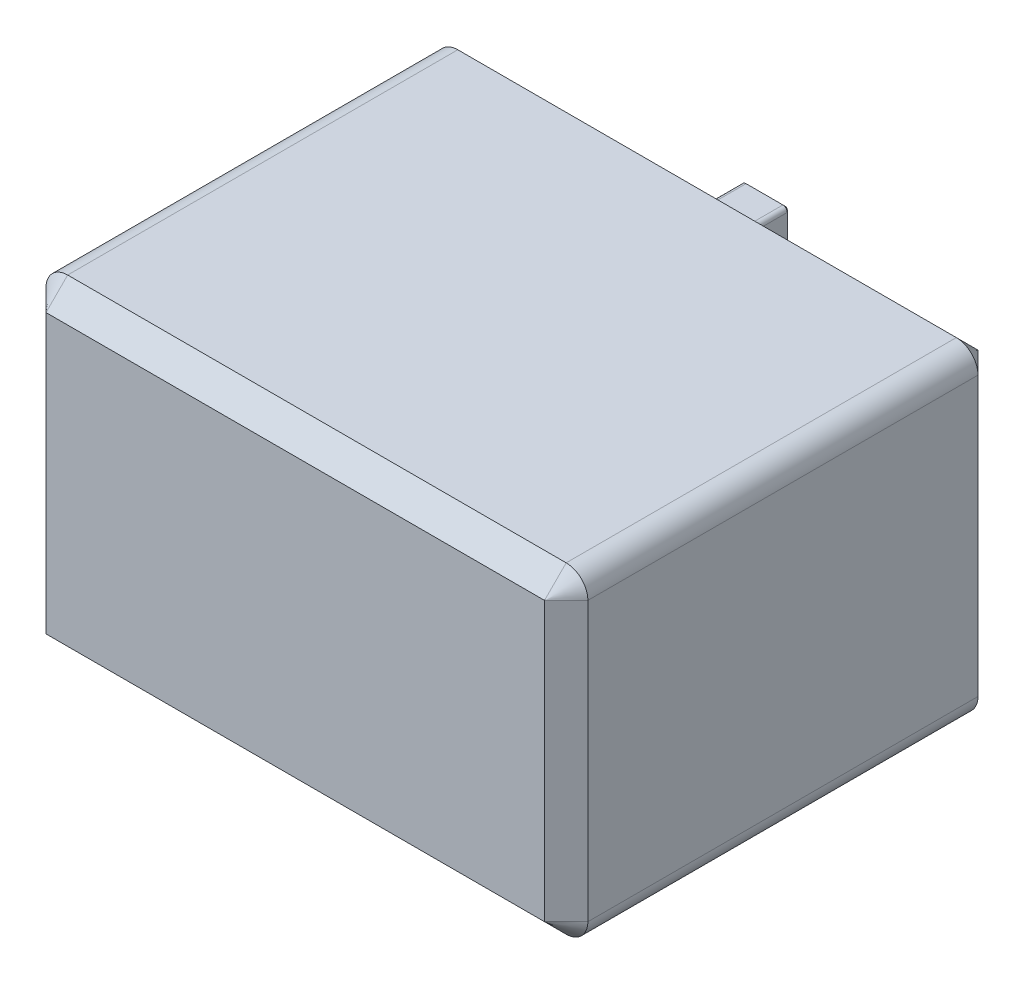
SolidWorks part; units mm, degrees
material "6061 Alloy"
ref_plane "Front Plane" through (0, 0, 0) normal (0, 0, 1) x (1, 0, 0)
ref_plane "Top Plane" through (0, 0, 0) normal (0, 1, 0) x (1, 0, 0)
ref_plane "Right Plane" through (0, 0, 0) normal (1, 0, 0) x (0, 0, -1)
sketch "main_features" plane through (0, 0, 0) normal (0, 0, 1) x (1, 0, 0)
  line L0 (0, 15.24) -> (0, 0) construction
  line L1 (6.15, 15.24) -> (-6.15, 15.24) construction
  line L2 (6.35, 15.04) -> (-6.35, 15.04) construction
  line L3 (12.5, 0.2) -> (-12.5, 0.2)
  line L4 (12.5, 0.2) -> (12.5, 15.04)
  line L5 (12.5, 15.04) -> (-12.5, 15.04)
  line L6 (-12.5, 0.2) -> (-12.5, 15.04)
  line L7 (12.5, 0.2) -> (-12.5, 15.04) construction
  line L8 (12.5, 15.04) -> (-12.5, 0.2) construction
  line L9 (-1.05, 13.69) -> (-1.05, 11.19) construction
  line L10 (1.05, 11.19) -> (-1.05, 11.19)
  line L12 (1.05, 11.19) -> (1.05, 13.69)
  line L13 (1.05, 13.69) -> (-1.05, 13.69)
  line L14 (-1.05, 11.19) -> (-1.05, 13.69)
  line L15 (1.05, 11.19) -> (-1.05, 13.69) construction
  line L16 (1.05, 13.69) -> (-1.05, 11.19) construction
  point P5 (0, 7.62)
  point P14 (0, 12.44)
  dimension "D1" = 25
extrude "peg" add sketch "main_features" against normal offset from surface (1.75 mm away) 0.25 contours L10 L13 region at (0, 12.44, 0)
extrude "block" add sketch "Sketch1<3>" along normal blind 20 contours L6 L5 L4 L3
sketch "Sketch1<3>" plane through (0, 0, 0) normal (0, 0, 1) x (1, 0, 0) same geometry as "main_features"
fillet "rounded_peg_edges" radius 0.2 4 edges at (1.05, 11.19, -0.875) (1.05, 13.69, -0.875) (-1.05, 11.19, -0.875) (-1.05, 13.69, -0.875)
fillet "rounded_block_edges" radius 1 4 edges at (12.5, 0.2, 10) (12.5, 15.04, 10) (-12.5, 15.04, 10) (-12.5, 0.2, 10)
chamfer "break_peg_edges" distance 0.1 angle 45 8 edges at (0.9914, 13.6314, -1.75) (0, 13.69, -1.75) (-0.9914, 13.6314, -1.75) (-1.05, 12.44, -1.75) (-0.9914, 11.2486, -1.75) (0, 11.19, -1.75) (0.9914, 11.2486, -1.75) (1.05, 12.44, -1.75)
chamfer "break_block_edges" distance 1 angle 45 16 edges at (0, 15.04, 0) (12.2071, 14.7471, 0) (-12.2071, 14.7471, 0) (12.5, 7.62, 0) (-12.5, 7.62, 0) (12.2071, 0.4929, 0) (-12.2071, 0.4929, 0) (0, 0.2, 0) (0, 0.2, 20) (12.2071, 0.4929, 20) (-12.2071, 0.4929, 20) (12.5, 7.62, 20) (-12.5, 7.62, 20) (12.2071, 14.7471, 20) (-12.2071, 14.7471, 20) (0, 15.04, 20)
